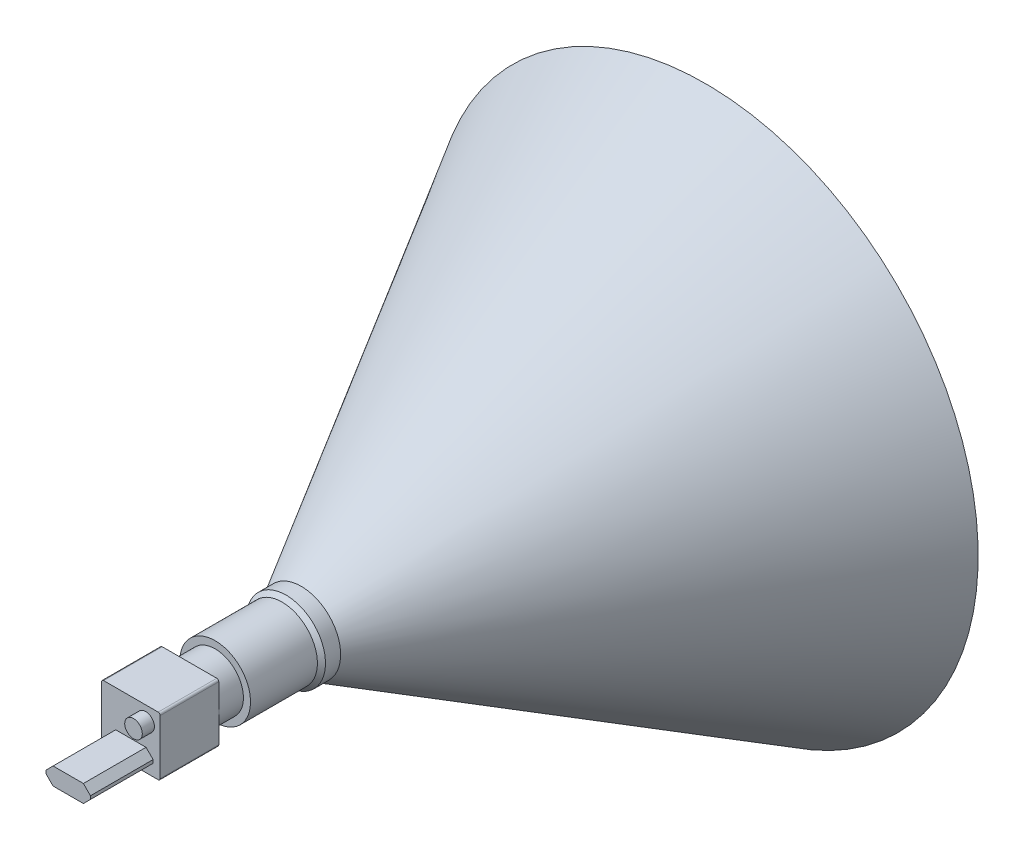
SolidWorks part; units mm, degrees
ref_plane "前视基准面" through (0, 0, 0) normal (0, 0, 1) x (1, 0, 0)
ref_plane "上视基准面" through (0, 0, 0) normal (0, 1, 0) x (1, 0, 0)
ref_plane "右视基准面" through (0, 0, 0) normal (1, 0, 0) x (0, 0, -1)
sketch "草图1" plane through (0, 0, 0) normal (0, 1, 0) x (1, 0, 0)
  line L1 (-14.5, 14.5) -> (14.5, 14.5)
  line L2 (-14.5, 14.5) -> (-14.5, -14.5)
  line L3 (-14.5, -14.5) -> (14.5, -14.5)
  line L4 (14.5, 14.5) -> (14.5, -14.5)
  line L5 (-14.5, 14.5) -> (14.5, -14.5) construction
  line L6 (-14.5, -14.5) -> (14.5, 14.5) construction
  point P0 (0, 0)
  dimension "D1" = 29
  dimension "D2" = 29
extrude "凸台-拉伸1" add sketch "草图1" along normal blind 29
sketch "草图2" plane through (0, 0, 0) normal (0, -1, 0) x (1, 0, 0)
  line L0 (14.5, -14.5) -> (-14.5, -14.5) construction
  line L1 (-14.5, -14.5) -> (-14.5, 14.5) construction
  line L2 (14.5, 14.5) -> (14.5, -14.5) construction
  line L3 (-14.5, 14.5) -> (14.5, 14.5) construction
  circle A0 centre (-10, -11.5) radius 1.7
  circle A1 centre (10, -11.5) radius 1.7
  circle A2 centre (0, 12) radius 1.7
  dimension "D1" = 3.4
  dimension "D2" = 3.4
  dimension "D3" = 3.4
  dimension "D4" = 3
  dimension "D5" = 4.5
  dimension "D6" = 4.5
  dimension "D7" = 2.5
extrude "切除-拉伸1" cut sketch "草图2" against normal blind 4
sketch "草图3" plane through (0, 0, -14.5) normal (0, 0, -1) x (-1, 0, 0)
  line L0 (-14.5, 0) -> (14.5, 0) construction
  line L1 (14.5, 29) -> (14.5, 0) construction
  circle A0 centre (0, 14.5) radius 14
  dimension "D1" = 28
  dimension "D2" = 14.5
  dimension "D3" = 14.5
extrude "凸台-拉伸2" add sketch "草图3" along normal blind 12.7
sketch "草图4" plane through (0, 0, -27.2) normal (0, 0, -1) x (-1, 0, 0)
  circle A0 centre (0, 14.5) radius 17.5
  dimension "D1" = 35
extrude "凸台-拉伸3" add sketch "草图4" along normal blind 32.6
sketch "草图6" plane through (0, 0, -59.8) normal (0, 0, -1) x (-1, 0, 0)
  circle A0 centre (0, 14.5) radius 19.5
  dimension "D1" = 39
extrude "凸台-拉伸4" add sketch "草图6" along normal blind 10
chamfer "倒角1" distance 2.5 angle 45 1 edges at (-19.5, 14.5, -59.8)
fillet "圆角1" radius 1 4 edges at (14.5, 0, 0) (-14.5, 0, 0) (-14.5, 29, 0) (14.5, 29, 0)
sketch "草图7" plane through (0, 0, 14.5) normal (0, 0, 1) x (1, 0, 0)
  line L0 (-13.5, 0) -> (13.5, 0) construction
  line L1 (-11, 10.9) -> (11, 10.9)
  line L2 (-11, 10.9) -> (-11, 2.3)
  line L3 (-11, 2.3) -> (11, 2.3)
  line L4 (11, 10.9) -> (11, 2.3)
  line L5 (-14.5, 28) -> (-14.5, 1) construction
  dimension "D1" = 2.3
  dimension "D2" = 8.6
  dimension "D3" = 22
  dimension "D4" = 3.5
extrude "凸台-拉伸5" add sketch "草图7" along normal blind 31
sketch "草图8" plane through (0, 0, 14.5) normal (0, 0, 1) x (1, 0, 0)
  line L0 (14.5, 28) -> (14.5, 1) construction
  line L1 (-13.5, 29) -> (13.5, 29) construction
  circle A0 centre (7.3, 21.8) radius 4.35
  dimension "D1" = 8.7
  dimension "D2" = 7.2
  dimension "D3" = 7.2
extrude "凸台-拉伸6" add sketch "草图8" along normal blind 6
chamfer "倒角2" distance 3.5 angle 45 4 edges at (11, 2.3, 30) (11, 10.9, 30) (-11, 2.3, 30) (-11, 10.9, 30)
sketch "草图10" plane through (0, 0, 0) normal (1, 0, 0) x (0, 0, -1)
  line L0 (69.8, 14.5) -> (104.4653, 14.5) construction
  line L1 (69.8, -5) -> (69.8, 34) construction
  line L2 (69.8, 34) -> (269.8, 149.4701)
  dimension "D1" = 120
  dimension "D2" = 200
surface "曲面-旋转1" sketch "草图10" parameters "D1"=360
sketch "草图11" plane through (0, 29, 0) normal (0, 1, 0) x (1, 0, 0)
  line L0 (0, -14.5) -> (0, 14.5) construction
  line L1 (-13.5, -14.5) -> (13.5, -14.5) construction
  line L2 (13.5, 14.5) -> (-13.5, 14.5) construction
